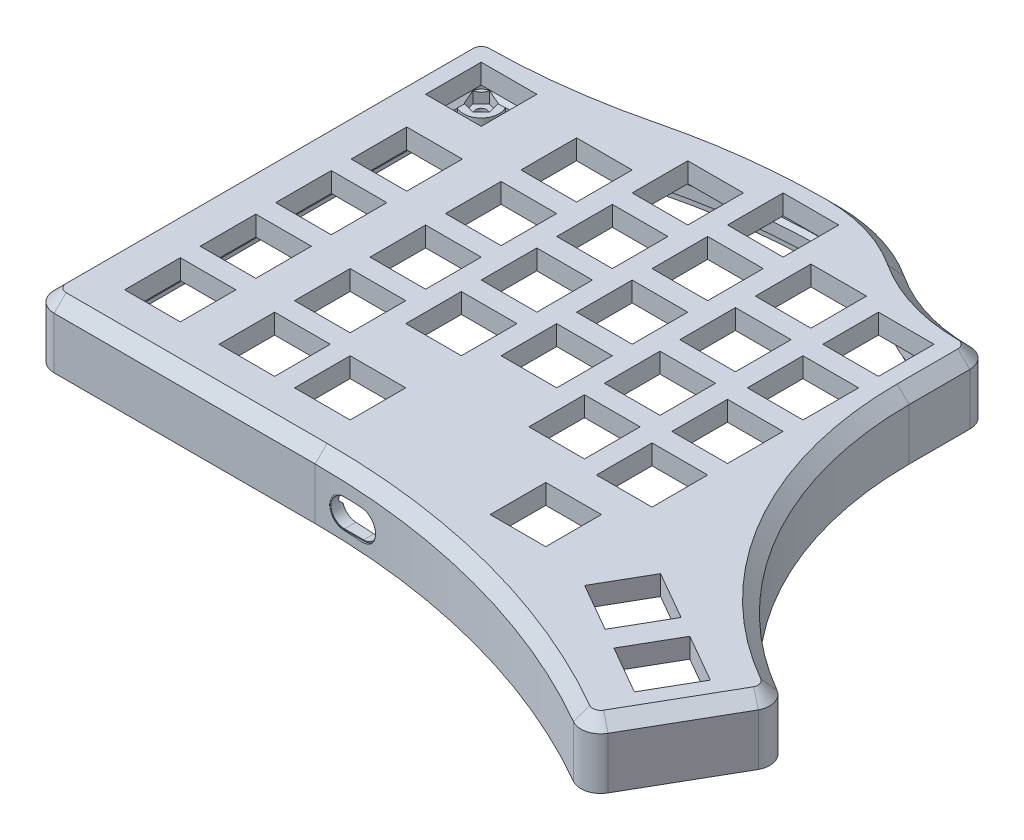
SolidWorks part; units mm, degrees
ref_plane "Front Plane" through (0, 0, 0) normal (0, 0, 1) x (1, 0, 0)
ref_plane "Top Plane" through (0, 0, 0) normal (0, 1, 0) x (1, 0, 0)
ref_plane "Right Plane" through (0, 0, 0) normal (1, 0, 0) x (0, 0, -1)
sketch "Main" plane through (0, 0, 0) normal (0, 1, 0) x (1, 0, 0)
  line L0 (6.4754, 3.5) -> (12.8, 6.5) construction
  line L1 (0, 0) -> (18, 0) construction
  line L2 (0, 0) -> (0, 18) construction
  line L3 (0, 18) -> (18, 18) construction
  line L4 (18, 0) -> (18, 18) construction
  line L5 (2, 16) -> (16, 16)
  line L6 (2, 16) -> (2, 2)
  line L7 (2, 2) -> (16, 2)
  line L8 (16, 16) -> (16, 2)
  line L18 (9, 9) -> (6.4754, 3.5) construction
  line L20 (9, 9) -> (12.8, 6.5) construction
  line L22 (25.4754, 12.5) -> (31.8, 15.5) construction
  line L23 (19, 9) -> (37, 9) construction
  line L24 (19, 9) -> (19, 27) construction
  line L25 (19, 27) -> (37, 27) construction
  line L26 (37, 9) -> (37, 27) construction
  line L27 (21, 25) -> (35, 25)
  line L28 (21, 25) -> (21, 11)
  line L29 (21, 11) -> (35, 11)
  line L30 (35, 25) -> (35, 11)
  line L31 (28, 18) -> (25.4754, 12.5) construction
  line L32 (28, 18) -> (31.8, 15.5) construction
  line L33 (44.4754, 17.5) -> (50.8, 20.5) construction
  line L34 (38, 14) -> (56, 14) construction
  line L35 (38, 14) -> (38, 32) construction
  line L36 (38, 32) -> (56, 32) construction
  line L37 (56, 14) -> (56, 32) construction
  line L38 (40, 30) -> (54, 30)
  line L39 (40, 30) -> (40, 16)
  line L40 (40, 16) -> (54, 16)
  line L41 (54, 30) -> (54, 16)
  line L42 (47, 23) -> (44.4754, 17.5) construction
  line L43 (47, 23) -> (50.8, 20.5) construction
  line L44 (63.4754, 5.5) -> (69.8, 8.5) construction
  line L45 (57, 2) -> (75, 2) construction
  line L46 (57, 2) -> (57, 20) construction
  line L47 (57, 20) -> (75, 20) construction
  line L48 (75, 2) -> (75, 20) construction
  line L49 (59, 18) -> (73, 18)
  line L50 (59, 18) -> (59, 4)
  line L51 (59, 4) -> (73, 4)
  line L52 (73, 18) -> (73, 4)
  line L53 (66, 11) -> (63.4754, 5.5) construction
  line L54 (66, 11) -> (69.8, 8.5) construction
  line L55 (82.4754, 3.5) -> (88.8, 6.5) construction
  line L56 (76, 0) -> (94, 0) construction
  line L57 (76, 0) -> (76, 18) construction
  line L58 (76, 18) -> (94, 18) construction
  line L59 (94, 0) -> (94, 18) construction
  line L60 (78, 16) -> (92, 16)
  line L61 (78, 16) -> (78, 2)
  line L62 (78, 2) -> (92, 2)
  line L63 (92, 16) -> (92, 2)
  line L64 (85, 9) -> (82.4754, 3.5) construction
  line L65 (85, 9) -> (88.8, 6.5) construction
  line L88 (2, -3) -> (16, -3)
  line L89 (2, -3) -> (2, -17)
  line L90 (2, -17) -> (16, -17)
  line L91 (16, -3) -> (16, -17)
  line L92 (21, 6) -> (35, 6)
  line L93 (21, 6) -> (21, -8)
  line L94 (21, -8) -> (35, -8)
  line L95 (35, 6) -> (35, -8)
  line L96 (40, 11) -> (54, 11)
  line L97 (40, 11) -> (40, -3)
  line L98 (40, -3) -> (54, -3)
  line L99 (54, 11) -> (54, -3)
  line L100 (59, -1) -> (73, -1)
  line L101 (59, -1) -> (59, -15)
  line L102 (59, -15) -> (73, -15)
  line L103 (73, -1) -> (73, -15)
  line L104 (78, -3) -> (92, -3)
  line L105 (78, -3) -> (78, -17)
  line L106 (78, -17) -> (92, -17)
  line L107 (92, -3) -> (92, -17)
  line L116 (6.4754, -15.5) -> (12.8, -12.5) construction
  line L117 (0, -19) -> (18, -19) construction
  line L118 (0, -19) -> (0, -1) construction
  line L119 (0, -1) -> (18, -1) construction
  line L120 (18, -19) -> (18, -1) construction
  line L121 (9, -10) -> (6.4754, -15.5) construction
  line L122 (9, -10) -> (12.8, -12.5) construction
  line L123 (25.4754, -6.5) -> (31.8, -3.5) construction
  line L124 (19, -10) -> (37, -10) construction
  line L125 (19, -10) -> (19, 8) construction
  line L126 (19, 8) -> (37, 8) construction
  line L127 (37, -10) -> (37, 8) construction
  line L128 (28, -1) -> (25.4754, -6.5) construction
  line L129 (28, -1) -> (31.8, -3.5) construction
  line L130 (44.4754, -1.5) -> (50.8, 1.5) construction
  line L131 (38, -5) -> (56, -5) construction
  line L132 (38, -5) -> (38, 13) construction
  line L133 (38, 13) -> (56, 13) construction
  line L134 (56, -5) -> (56, 13) construction
  line L135 (47, 4) -> (44.4754, -1.5) construction
  line L136 (47, 4) -> (50.8, 1.5) construction
  line L137 (63.4754, -13.5) -> (69.8, -10.5) construction
  line L138 (57, -17) -> (75, -17) construction
  line L139 (57, -17) -> (57, 1) construction
  line L140 (57, 1) -> (75, 1) construction
  line L141 (75, -17) -> (75, 1) construction
  line L142 (66, -8) -> (63.4754, -13.5) construction
  line L143 (66, -8) -> (69.8, -10.5) construction
  line L144 (82.4754, -15.5) -> (88.8, -12.5) construction
  line L145 (76, -19) -> (94, -19) construction
  line L146 (76, -19) -> (76, -1) construction
  line L147 (76, -1) -> (94, -1) construction
  line L148 (94, -19) -> (94, -1) construction
  line L149 (85, -10) -> (82.4754, -15.5) construction
  line L150 (85, -10) -> (88.8, -12.5) construction
  line L165 (2, -22) -> (16, -22)
  line L166 (2, -22) -> (2, -36)
  line L167 (2, -36) -> (16, -36)
  line L168 (16, -22) -> (16, -36)
  line L169 (21, -13) -> (35, -13)
  line L170 (21, -13) -> (21, -27)
  line L171 (21, -27) -> (35, -27)
  line L172 (35, -13) -> (35, -27)
  line L173 (40, -8) -> (54, -8)
  line L174 (40, -8) -> (40, -22)
  line L175 (40, -22) -> (54, -22)
  line L176 (54, -8) -> (54, -22)
  line L177 (59, -20) -> (73, -20)
  line L178 (59, -20) -> (59, -34)
  line L179 (59, -34) -> (73, -34)
  line L180 (73, -20) -> (73, -34)
  line L181 (78, -22) -> (92, -22)
  line L182 (78, -22) -> (78, -36)
  line L183 (78, -36) -> (92, -36)
  line L184 (92, -22) -> (92, -36)
  line L193 (6.4754, -34.5) -> (12.8, -31.5) construction
  line L194 (0, -38) -> (18, -38) construction
  line L195 (0, -38) -> (0, -20) construction
  line L196 (0, -20) -> (18, -20) construction
  line L197 (18, -38) -> (18, -20) construction
  line L198 (9, -29) -> (6.4754, -34.5) construction
  line L199 (9, -29) -> (12.8, -31.5) construction
  line L200 (25.4754, -25.5) -> (31.8, -22.5) construction
  line L201 (19, -29) -> (37, -29) construction
  line L202 (19, -29) -> (19, -11) construction
  line L203 (19, -11) -> (37, -11) construction
  line L204 (37, -29) -> (37, -11) construction
  line L205 (28, -20) -> (25.4754, -25.5) construction
  line L206 (28, -20) -> (31.8, -22.5) construction
  line L207 (44.4754, -20.5) -> (50.8, -17.5) construction
  line L208 (38, -24) -> (56, -24) construction
  line L209 (38, -24) -> (38, -6) construction
  line L210 (38, -6) -> (56, -6) construction
  line L211 (56, -24) -> (56, -6) construction
  line L212 (47, -15) -> (44.4754, -20.5) construction
  line L213 (47, -15) -> (50.8, -17.5) construction
  line L214 (63.4754, -32.5) -> (69.8, -29.5) construction
  line L215 (57, -36) -> (75, -36) construction
  line L216 (57, -36) -> (57, -18) construction
  line L217 (57, -18) -> (75, -18) construction
  line L218 (75, -36) -> (75, -18) construction
  line L219 (66, -27) -> (63.4754, -32.5) construction
  line L220 (66, -27) -> (69.8, -29.5) construction
  line L221 (82.4754, -34.5) -> (88.8, -31.5) construction
  line L222 (76, -38) -> (94, -38) construction
  line L223 (76, -38) -> (76, -20) construction
  line L224 (76, -20) -> (94, -20) construction
  line L225 (94, -38) -> (94, -20) construction
  line L226 (85, -29) -> (82.4754, -34.5) construction
  line L227 (85, -29) -> (88.8, -31.5) construction
  line L242 (2, -41) -> (16, -41)
  line L243 (2, -41) -> (2, -55)
  line L244 (2, -55) -> (16, -55)
  line L245 (16, -41) -> (16, -55)
  line L246 (21, -32) -> (35, -32)
  line L247 (21, -32) -> (21, -46)
  line L248 (21, -46) -> (35, -46)
  line L249 (35, -32) -> (35, -46)
  line L250 (40, -27) -> (54, -27)
  line L251 (40, -27) -> (40, -41)
  line L252 (40, -41) -> (54, -41)
  line L253 (54, -27) -> (54, -41)
  line L254 (59, -39) -> (73, -39)
  line L255 (59, -39) -> (59, -53)
  line L256 (59, -53) -> (73, -53)
  line L257 (73, -39) -> (73, -53)
  line L258 (78, -41) -> (92, -41)
  line L259 (78, -41) -> (78, -55)
  line L260 (78, -55) -> (92, -55)
  line L261 (92, -41) -> (92, -55)
  line L270 (6.4754, -53.5) -> (12.8, -50.5) construction
  line L271 (0, -57) -> (18, -57) construction
  line L272 (0, -57) -> (0, -39) construction
  line L273 (0, -39) -> (18, -39) construction
  line L274 (18, -57) -> (18, -39) construction
  line L275 (9, -48) -> (6.4754, -53.5) construction
  line L276 (9, -48) -> (12.8, -50.5) construction
  line L277 (25.4754, -44.5) -> (31.8, -41.5) construction
  line L278 (19, -48) -> (37, -48) construction
  line L279 (19, -48) -> (19, -30) construction
  line L280 (19, -30) -> (37, -30) construction
  line L281 (37, -48) -> (37, -30) construction
  line L282 (28, -39) -> (25.4754, -44.5) construction
  line L283 (28, -39) -> (31.8, -41.5) construction
  line L284 (44.4754, -39.5) -> (50.8, -36.5) construction
  line L285 (38, -43) -> (56, -43) construction
  line L286 (38, -43) -> (38, -25) construction
  line L287 (38, -25) -> (56, -25) construction
  line L288 (56, -43) -> (56, -25) construction
  line L289 (47, -34) -> (44.4754, -39.5) construction
  line L290 (47, -34) -> (50.8, -36.5) construction
  line L291 (63.4754, -51.5) -> (69.8, -48.5) construction
  line L292 (57, -55) -> (75, -55) construction
  line L293 (57, -55) -> (57, -37) construction
  line L294 (57, -37) -> (75, -37) construction
  line L295 (75, -55) -> (75, -37) construction
  line L296 (66, -46) -> (63.4754, -51.5) construction
  line L297 (66, -46) -> (69.8, -48.5) construction
  line L298 (82.4754, -53.5) -> (88.8, -50.5) construction
  line L299 (76, -57) -> (94, -57) construction
  line L300 (76, -57) -> (76, -39) construction
  line L301 (76, -39) -> (94, -39) construction
  line L302 (94, -57) -> (94, -39) construction
  line L303 (85, -48) -> (82.4754, -53.5) construction
  line L304 (85, -48) -> (88.8, -50.5) construction
  line L312 (6.4754, -72.5) -> (12.8, -69.5) construction
  line L313 (0, -76) -> (18, -76) construction
  line L314 (0, -76) -> (0, -58) construction
  line L315 (0, -58) -> (18, -58) construction
  line L316 (18, -76) -> (18, -58) construction
  line L317 (2, -60) -> (16, -60)
  line L318 (2, -60) -> (2, -74)
  line L323 (21, -60) -> (35, -60)
  line L324 (21, -60) -> (21, -74)
  line L325 (21, -74) -> (35, -74)
  line L326 (35, -60) -> (35, -74)
  line L327 (25.4754, -72.5) -> (31.8, -69.5) construction
  line L328 (19, -76) -> (37, -76) construction
  line L329 (19, -76) -> (19, -58) construction
  line L330 (-22.0246, 8) -> (-15.7, 11) construction
  line L331 (-28.5, 4.5) -> (-10.5, 4.5) construction
  line L332 (-28.5, 4.5) -> (-28.5, 22.5) construction
  line L333 (-28.5, 22.5) -> (-10.5, 22.5) construction
  line L334 (-10.5, 4.5) -> (-10.5, 22.5) construction
  line L335 (-26.5, 20.5) -> (-12.5, 20.5)
  line L336 (-26.5, 20.5) -> (-26.5, 6.5)
  line L337 (-26.5, 6.5) -> (-12.5, 6.5)
  line L338 (-12.5, 20.5) -> (-12.5, 6.5)
  line L339 (-19.5, 13.5) -> (-22.0246, 8) construction
  line L340 (-19.5, 13.5) -> (-15.7, 11) construction
  line L341 (-21.75, -41) -> (-7.75, -41)
  line L342 (-21.75, -41) -> (-21.75, -55)
  line L343 (-21.75, -55) -> (-7.75, -55)
  line L344 (-7.75, -41) -> (-7.75, -55)
  line L345 (-17.2746, -53.5) -> (-10.95, -50.5) construction
  line L346 (-28.5, -57) -> (-1, -57) construction
  line L347 (-28.5, -57) -> (-28.5, -39) construction
  line L348 (-28.5, -39) -> (-1, -39) construction
  line L349 (-1, -57) -> (-1, -39) construction
  line L350 (-14.75, -48) -> (-17.2746, -53.5) construction
  line L351 (-14.75, -48) -> (-10.95, -50.5) construction
  line L352 (-21.75, -22) -> (-7.75, -22)
  line L353 (-21.75, -22) -> (-21.75, -36)
  line L354 (2, -74) -> (16, -74)
  line L355 (16, -60) -> (16, -74)
  line L356 (9, -67) -> (6.4754, -72.5) construction
  line L357 (9, -67) -> (12.8, -69.5) construction
  line L358 (-17.2746, -72.5) -> (-10.95, -69.5) construction
  line L359 (-28.5, -76) -> (-1, -76) construction
  line L360 (-28.5, -76) -> (-28.5, -58) construction
  line L361 (-28.5, -58) -> (-1, -58) construction
  line L362 (-1, -76) -> (-1, -58) construction
  line L363 (-21.75, -60) -> (-7.75, -60)
  line L364 (-21.75, -60) -> (-21.75, -74)
  line L365 (-21.75, -74) -> (-7.75, -74)
  line L366 (-7.75, -60) -> (-7.75, -74)
  line L367 (-14.75, -67) -> (-17.2746, -72.5) construction
  line L368 (-14.75, -67) -> (-10.95, -69.5) construction
  line L369 (-21.75, -36) -> (-7.75, -36)
  line L370 (-7.75, -22) -> (-7.75, -36)
  line L371 (-17.2746, -34.5) -> (-10.95, -31.5) construction
  line L372 (-28.5, -38) -> (-1, -38) construction
  line L373 (-28.5, -38) -> (-28.5, -20) construction
  line L374 (-28.5, -20) -> (-1, -20) construction
  line L375 (-1, -38) -> (-1, -20) construction
  line L376 (-14.75, -29) -> (-17.2746, -34.5) construction
  line L377 (-14.75, -29) -> (-10.95, -31.5) construction
  line L378 (-21.75, -3) -> (-7.75, -3)
  line L379 (-21.75, -3) -> (-21.75, -17)
  line L380 (-21.75, -17) -> (-7.75, -17)
  line L381 (-7.75, -3) -> (-7.75, -17)
  line L382 (-17.2746, -15.5) -> (-10.95, -12.5) construction
  line L383 (-28.5, -19) -> (-1, -19) construction
  line L384 (-28.5, -19) -> (-28.5, -1) construction
  line L385 (-28.5, -1) -> (-1, -1) construction
  line L386 (-1, -19) -> (-1, -1) construction
  line L387 (-14.75, -10) -> (-17.2746, -15.5) construction
  line L388 (-14.75, -10) -> (-10.95, -12.5) construction
  line L393 (109.2068, -61.578) -> (124.8116, -70.5498) construction
  line L394 (109.2068, -61.578) -> (95.5, -85.4186) construction
  line L398 (124.8116, -70.5498) -> (111.1047, -94.3903) construction
  line L402 (77.7254, -75.5) -> (84.05, -72.5) construction
  line L403 (66.5, -79) -> (94, -79) construction
  line L404 (66.5, -79) -> (66.5, -61) construction
  line L405 (66.5, -61) -> (94, -61) construction
  line L406 (94, -79) -> (94, -61) construction
  line L407 (73.25, -63) -> (87.25, -63)
  line L408 (73.25, -63) -> (73.25, -77)
  line L409 (73.25, -77) -> (87.25, -77)
  line L410 (87.25, -63) -> (87.25, -77)
  line L411 (80.25, -70) -> (77.7254, -75.5) construction
  line L412 (80.25, -70) -> (84.05, -72.5) construction
  line L413 (95.5, -85.4186) -> (111.1047, -94.3903) construction
  line L414 (95.5, -85.4186) -> (124.8116, -70.5498) construction
  line L415 (80.25, -130) -> (110.1558, -77.9842) construction
  line L416 (107.5763, -68.4267) -> (119.7133, -75.4047)
  line L417 (107.5763, -68.4267) -> (100.5983, -80.5637)
  line L418 (119.7133, -75.4047) -> (112.7353, -87.5417)
  line L419 (100.5983, -80.5637) -> (112.7353, -87.5417)
  line L420 (107.5763, -68.4267) -> (112.7353, -87.5417) construction
  line L421 (105.2258, -81.494) -> (110.1558, -77.9842) construction
  line L422 (110.1558, -77.9842) -> (112.204, -82.0455) construction
  line L423 (112.204, -82.0455) -> (105.2258, -81.494) construction
  line L424 (126.5454, -71.5466) -> (142.1502, -80.5184) construction
  line L425 (126.5454, -71.5466) -> (112.8386, -95.3872) construction
  line L426 (142.1502, -80.5184) -> (128.4433, -104.3589) construction
  line L427 (112.8386, -95.3872) -> (128.4433, -104.3589) construction
  line L428 (112.8386, -95.3872) -> (142.1502, -80.5184) construction
  line L430 (124.9149, -78.3953) -> (137.0519, -85.3733)
  line L431 (124.9149, -78.3953) -> (117.9369, -90.5323)
  line L432 (137.0519, -85.3733) -> (130.0739, -97.5103)
  line L433 (117.9369, -90.5323) -> (130.0739, -97.5103)
  line L434 (124.9149, -78.3953) -> (130.0739, -97.5103) construction
  line L435 (122.5644, -91.4626) -> (127.4944, -87.9528) construction
  line L436 (127.4944, -87.9528) -> (129.5426, -92.0141) construction
  line L437 (129.5426, -92.0141) -> (122.5644, -91.4626) construction
  line L448 (19, -58) -> (37, -58) construction
  line L449 (37, -76) -> (37, -58) construction
  line L450 (28, -67) -> (25.4754, -72.5) construction
  line L451 (28, -67) -> (31.8, -69.5) construction
  circle A0 centre (9, 9) radius 2 construction
  circle A1 centre (6.4754, 3.5) radius 1.5 construction
  circle A2 centre (12.8, 6.5) radius 1.5 construction
  circle A6 centre (28, 18) radius 2 construction
  circle A7 centre (25.4754, 12.5) radius 1.5 construction
  circle A8 centre (31.8, 15.5) radius 1.5 construction
  circle A9 centre (47, 23) radius 2 construction
  circle A10 centre (44.4754, 17.5) radius 1.5 construction
  circle A11 centre (50.8, 20.5) radius 1.5 construction
  circle A12 centre (66, 11) radius 2 construction
  circle A13 centre (63.4754, 5.5) radius 1.5 construction
  circle A14 centre (69.8, 8.5) radius 1.5 construction
  circle A15 centre (85, 9) radius 2 construction
  circle A16 centre (82.4754, 3.5) radius 1.5 construction
  circle A17 centre (88.8, 6.5) radius 1.5 construction
  circle A24 centre (9, -10) radius 2 construction
  circle A25 centre (6.4754, -15.5) radius 1.5 construction
  circle A26 centre (12.8, -12.5) radius 1.5 construction
  circle A27 centre (28, -1) radius 2 construction
  circle A28 centre (25.4754, -6.5) radius 1.5 construction
  circle A29 centre (31.8, -3.5) radius 1.5 construction
  circle A30 centre (47, 4) radius 2 construction
  circle A31 centre (44.4754, -1.5) radius 1.5 construction
  circle A32 centre (50.8, 1.5) radius 1.5 construction
  circle A33 centre (66, -8) radius 2 construction
  circle A34 centre (63.4754, -13.5) radius 1.5 construction
  circle A35 centre (69.8, -10.5) radius 1.5 construction
  circle A36 centre (85, -10) radius 2 construction
  circle A37 centre (82.4754, -15.5) radius 1.5 construction
  circle A38 centre (88.8, -12.5) radius 1.5 construction
  circle A45 centre (9, -29) radius 2 construction
  circle A46 centre (6.4754, -34.5) radius 1.5 construction
  circle A47 centre (12.8, -31.5) radius 1.5 construction
  circle A48 centre (28, -20) radius 2 construction
  circle A49 centre (25.4754, -25.5) radius 1.5 construction
  circle A50 centre (31.8, -22.5) radius 1.5 construction
  circle A51 centre (47, -15) radius 2 construction
  circle A52 centre (44.4754, -20.5) radius 1.5 construction
  circle A53 centre (50.8, -17.5) radius 1.5 construction
  circle A54 centre (66, -27) radius 2 construction
  circle A55 centre (63.4754, -32.5) radius 1.5 construction
  circle A56 centre (69.8, -29.5) radius 1.5 construction
  circle A57 centre (85, -29) radius 2 construction
  circle A58 centre (82.4754, -34.5) radius 1.5 construction
  circle A59 centre (88.8, -31.5) radius 1.5 construction
  circle A63 centre (9, -67) radius 2 construction
  circle A64 centre (6.4754, -72.5) radius 1.5 construction
  circle A65 centre (12.8, -69.5) radius 1.5 construction
  circle A66 centre (9, -48) radius 2 construction
  circle A67 centre (6.4754, -53.5) radius 1.5 construction
  circle A68 centre (12.8, -50.5) radius 1.5 construction
  circle A69 centre (28, -39) radius 2 construction
  circle A70 centre (25.4754, -44.5) radius 1.5 construction
  circle A71 centre (31.8, -41.5) radius 1.5 construction
  circle A72 centre (47, -34) radius 2 construction
  circle A73 centre (44.4754, -39.5) radius 1.5 construction
  circle A74 centre (50.8, -36.5) radius 1.5 construction
  circle A75 centre (66, -46) radius 2 construction
  circle A76 centre (63.4754, -51.5) radius 1.5 construction
  circle A77 centre (69.8, -48.5) radius 1.5 construction
  circle A78 centre (85, -48) radius 2 construction
  circle A79 centre (82.4754, -53.5) radius 1.5 construction
  circle A80 centre (88.8, -50.5) radius 1.5 construction
  circle A81 centre (-14.75, -67) radius 2 construction
  circle A82 centre (-17.2746, -72.5) radius 1.5 construction
  circle A83 centre (-10.95, -69.5) radius 1.5 construction
  circle A84 centre (28, -67) radius 2 construction
  circle A85 centre (25.4754, -72.5) radius 1.5 construction
  circle A86 centre (31.8, -69.5) radius 1.5 construction
  circle A87 centre (-19.5, 13.5) radius 2 construction
  circle A88 centre (-22.0246, 8) radius 1.5 construction
  circle A89 centre (-15.7, 11) radius 1.5 construction
  circle A90 centre (-14.75, -48) radius 2 construction
  circle A91 centre (-17.2746, -53.5) radius 1.5 construction
  circle A92 centre (-10.95, -50.5) radius 1.5 construction
  circle A93 centre (-14.75, -29) radius 2 construction
  circle A94 centre (-17.2746, -34.5) radius 1.5 construction
  circle A95 centre (-10.95, -31.5) radius 1.5 construction
  circle A96 centre (-14.75, -10) radius 2 construction
  circle A97 centre (-17.2746, -15.5) radius 1.5 construction
  circle A98 centre (-10.95, -12.5) radius 1.5 construction
  circle A102 centre (80.25, -70) radius 2 construction
  circle A103 centre (77.7254, -75.5) radius 1.5 construction
  circle A104 centre (84.05, -72.5) radius 1.5 construction
  circle A105 centre (80.25, -130) radius 60 construction
  circle A106 centre (110.1558, -77.9842) radius 2 construction
  circle A107 centre (105.2258, -81.494) radius 1.5 construction
  circle A108 centre (112.204, -82.0455) radius 1.5 construction
  circle A109 centre (127.4944, -87.9528) radius 2 construction
  circle A110 centre (122.5644, -91.4626) radius 1.5 construction
  circle A111 centre (129.5426, -92.0141) radius 1.5 construction
  circle A112 centre (62, -66) radius 1.5 construction
  point P9 (9, 16)
  point P10 (9, 18)
  point P11 (2, 9)
  point P12 (0, 9)
  point P30 (28, 25)
  point P31 (28, 27)
  point P32 (21, 18)
  point P33 (19, 18)
  point P46 (47, 30)
  point P47 (47, 32)
  point P48 (40, 23)
  point P49 (38, 23)
  point P64 (66, 18)
  point P65 (66, 20)
  point P66 (59, 11)
  point P67 (57, 11)
  point P82 (85, 16)
  point P83 (85, 18)
  point P84 (78, 9)
  point P85 (76, 9)
  point P102 (9, -60)
  point P103 (9, -58)
  point P104 (2, -67)
  point P105 (0, -67)
  point P124 (-14.75, -60)
  point P125 (-14.75, -58)
  point P126 (-21.75, -67)
  point P127 (-28.5, -67)
  point P297 (-19.5, 20.5)
  point P298 (-19.5, 22.5)
  point P299 (-26.5, 13.5)
  point P300 (-28.5, 13.5)
  point P423 (103.3024, -89.9045)
  point P444 (80.25, -63)
  point P445 (80.25, -61)
  point P446 (73.25, -70)
  point P447 (66.5, -70)
  dimension "D6" = 4
  dimension "D7" = 3
  dimension "D10" = 1
  dimension "D11" = 12
  dimension "D21" = 9.5
  dimension "D22" = 1.5
  dimension "D26" = 120
  dimension "D28" = 3
  dimension "D1" = 18
  dimension "D2" = 14
  dimension "D3" = 3.2
  dimension "D4" = 4.5
  dimension "D5" = 7
  dimension "D8" = 1
  dimension "D9" = 5
  dimension "D12" = 1
  dimension "D13" = 9
  dimension "D14" = 1
  dimension "D15" = 2
  dimension "D16" = 2
  dimension "D17" = 27.5
  dimension "D18" = 1
  dimension "D20" = 1
  dimension "D24" = 1
  dimension "D25" = 8
  dimension "D27" = 2
  dimension "D29" = 15
  dimension "D30" = 32
  dimension "D19" = 4
  dimension "D23" = 4
sketch "Sketch1" plane through (0, 0, 0) normal (0, 1, 0) x (1, 0, 0)
  line L0 (-33.5, 22.5) -> (-33.5, -80)
  line L1 (-28.5, -85) -> (37.2039, -85)
  line L2 (132.778, -106.8511) -> (146.594, -82.8206)
  line L3 (99, 2.7142) -> (99, 18)
  line L6 (-28.5, -76) -> (-1, -76) construction
  line L7 (-28.5, -76) -> (-28.5, -58) construction
  line L8 (144.6447, -76.1796) -> (94, -47.0621) construction
  line L9 (142.1502, -80.5184) -> (128.4433, -104.3589) construction
  line L10 (94, 0) -> (94, 18) construction
  line L11 (94, -57) -> (94, -39) construction
  line L12 (128.4433, -104.3589) -> (125.9512, -108.6936) construction
  line L13 (109.2068, -61.578) -> (124.8116, -70.5498) construction
  line L14 (125.9512, -108.6936) -> (74.3045, -79) construction
  line L15 (66.5, -79) -> (94, -79) construction
  line L16 (38, 32) -> (56, 32) construction
  line L17 (95.5, -85.4186) -> (111.1047, -94.3903) construction
  line L18 (47, 37) -> (47, 32) construction
  line L19 (47, 37) -> (-33.5, 37) construction
  line L20 (94, 23) -> (56, 23) construction
  line L21 (56, 14) -> (56, 32) construction
  line L22 (-31.5, 22.5) -> (-31.5, -80) construction
  line L24 (-28.5, -83) -> (37.2039, -83) construction
  line L25 (131.0441, -105.8542) -> (144.8356, -81.8665) construction
  line L26 (97, 2.7142) -> (97, 18) construction
  line L39 (107.5763, -68.4267) -> (119.7133, -75.4047)
  line L40 (-26.5, 20.5) -> (-12.5, 20.5)
  line L41 (-26.5, 20.5) -> (-26.5, 6.5)
  line L42 (-26.5, 6.5) -> (-12.5, 6.5)
  line L43 (-12.5, 20.5) -> (-12.5, 6.5)
  line L44 (-21.75, -3) -> (-7.75, -3)
  line L45 (-21.75, -3) -> (-21.75, -17)
  line L46 (-21.75, -17) -> (-7.75, -17)
  line L47 (-7.75, -3) -> (-7.75, -17)
  line L48 (-21.75, -22) -> (-7.75, -22)
  line L49 (-21.75, -22) -> (-21.75, -36)
  line L50 (-21.75, -36) -> (-7.75, -36)
  line L51 (-7.75, -22) -> (-7.75, -36)
  line L52 (-21.75, -41) -> (-7.75, -41)
  line L53 (-21.75, -41) -> (-21.75, -55)
  line L54 (-21.75, -55) -> (-7.75, -55)
  line L55 (-7.75, -41) -> (-7.75, -55)
  line L56 (-21.75, -60) -> (-7.75, -60)
  line L57 (-21.75, -60) -> (-21.75, -74)
  line L58 (-21.75, -74) -> (-7.75, -74)
  line L59 (-7.75, -60) -> (-7.75, -74)
  line L60 (2, 16) -> (16, 16)
  line L61 (2, 16) -> (2, 2)
  line L62 (2, 2) -> (16, 2)
  line L63 (16, 16) -> (16, 2)
  line L64 (2, -3) -> (16, -3)
  line L65 (2, -3) -> (2, -17)
  line L66 (2, -17) -> (16, -17)
  line L67 (16, -3) -> (16, -17)
  line L68 (2, -22) -> (16, -22)
  line L69 (2, -22) -> (2, -36)
  line L70 (2, -36) -> (16, -36)
  line L71 (16, -22) -> (16, -36)
  line L72 (2, -41) -> (16, -41)
  line L73 (2, -41) -> (2, -55)
  line L74 (2, -55) -> (16, -55)
  line L75 (16, -41) -> (16, -55)
  line L76 (2, -60) -> (16, -60)
  line L77 (2, -60) -> (2, -74)
  line L78 (2, -74) -> (16, -74)
  line L79 (16, -60) -> (16, -74)
  line L80 (21, -60) -> (35, -60)
  line L81 (21, -60) -> (21, -74)
  line L82 (21, -74) -> (35, -74)
  line L83 (35, -60) -> (35, -74)
  line L84 (21, -32) -> (35, -32)
  line L85 (21, -32) -> (21, -46)
  line L86 (21, -46) -> (35, -46)
  line L87 (35, -32) -> (35, -46)
  line L88 (21, 25) -> (35, 25)
  line L89 (21, 25) -> (21, 11)
  line L90 (21, 11) -> (35, 11)
  line L91 (35, 25) -> (35, 11)
  line L92 (21, 6) -> (35, 6)
  line L93 (21, 6) -> (21, -8)
  line L94 (21, -8) -> (35, -8)
  line L95 (35, 6) -> (35, -8)
  line L96 (21, -13) -> (35, -13)
  line L97 (21, -13) -> (21, -27)
  line L98 (21, -27) -> (35, -27)
  line L99 (35, -13) -> (35, -27)
  line L100 (40, 30) -> (54, 30)
  line L101 (40, 30) -> (40, 16)
  line L102 (40, 16) -> (54, 16)
  line L103 (54, 30) -> (54, 16)
  line L104 (40, 11) -> (54, 11)
  line L105 (40, 11) -> (40, -3)
  line L106 (40, -3) -> (54, -3)
  line L107 (54, 11) -> (54, -3)
  line L108 (40, -8) -> (54, -8)
  line L109 (40, -8) -> (40, -22)
  line L110 (40, -22) -> (54, -22)
  line L111 (54, -8) -> (54, -22)
  line L112 (40, -27) -> (54, -27)
  line L113 (40, -27) -> (40, -41)
  line L114 (40, -41) -> (54, -41)
  line L115 (54, -27) -> (54, -41)
  line L116 (59, 18) -> (73, 18)
  line L117 (59, 18) -> (59, 4)
  line L118 (59, 4) -> (73, 4)
  line L119 (73, 18) -> (73, 4)
  line L120 (78, 16) -> (92, 16)
  line L121 (78, 16) -> (78, 2)
  line L122 (78, 2) -> (92, 2)
  line L123 (92, 16) -> (92, 2)
  line L124 (59, -1) -> (73, -1)
  line L125 (59, -1) -> (59, -15)
  line L126 (59, -15) -> (73, -15)
  line L127 (73, -1) -> (73, -15)
  line L128 (78, -3) -> (92, -3)
  line L129 (78, -3) -> (78, -17)
  line L130 (78, -17) -> (92, -17)
  line L131 (92, -3) -> (92, -17)
  line L132 (59, -20) -> (73, -20)
  line L133 (59, -20) -> (59, -34)
  line L134 (59, -34) -> (73, -34)
  line L135 (73, -20) -> (73, -34)
  line L136 (78, -22) -> (92, -22)
  line L137 (78, -22) -> (78, -36)
  line L138 (78, -36) -> (92, -36)
  line L139 (92, -22) -> (92, -36)
  line L140 (59, -39) -> (73, -39)
  line L141 (59, -39) -> (59, -53)
  line L142 (59, -53) -> (73, -53)
  line L143 (73, -39) -> (73, -53)
  line L144 (78, -41) -> (92, -41)
  line L145 (78, -41) -> (78, -55)
  line L146 (78, -55) -> (92, -55)
  line L147 (92, -41) -> (92, -55)
  line L148 (73.25, -63) -> (87.25, -63)
  line L149 (73.25, -63) -> (73.25, -77)
  line L150 (73.25, -77) -> (87.25, -77)
  line L151 (87.25, -63) -> (87.25, -77)
  line L152 (107.5763, -68.4267) -> (100.5983, -80.5637)
  line L153 (119.7133, -75.4047) -> (112.7353, -87.5417)
  line L154 (100.5983, -80.5637) -> (112.7353, -87.5417)
  line L155 (124.9149, -78.3953) -> (137.0519, -85.3733)
  line L156 (124.9149, -78.3953) -> (117.9369, -90.5323)
  line L157 (137.0519, -85.3733) -> (130.0739, -97.5103)
  line L158 (117.9369, -90.5323) -> (130.0739, -97.5103)
  arc A0 (37.2039, -85) -> (125.9512, -108.6936) centre (37.2039, -263.0538) cw
  arc A4 (94, 23) -> (70.5, 30) centre (94, 65.9464) cw
  arc A5 (70.5, 30) -> (47, 37) centre (47, -5.9464) ccw
  arc A6 (47, 37) -> (8.1496, 32.2427) centre (47, -124.0147) ccw
  arc A7 (8.1496, 32.2427) -> (-28.5663, 27.4996) centre (-30.7009, 188.5001) cw
  arc A10 (125.9512, -108.6936) -> (132.778, -106.8511) centre (128.4433, -104.3589) ccw
  arc A11 (-33.5, -80) -> (-28.5, -85) centre (-28.5, -80) ccw
  arc A14 (146.594, -82.8206) -> (144.6447, -76.1796) centre (142.1502, -80.5184) ccw
  arc A15 (144.6447, -76.1796) -> (99, 2.7142) centre (190.0036, 2.7142) cw
  arc A16 (99, 18) -> (94, 23) centre (94, 18) ccw
  arc A17 (-33.5, 22.5) -> (-28.5663, 27.4996) centre (-28.5, 22.5) cw
  arc A18 (8.6321, 30.3018) -> (-28.5398, 25.4997) centre (-30.7009, 188.5001) cw construction
  arc A19 (-31.5, 22.5) -> (-28.5398, 25.4997) centre (-28.5, 22.5) cw construction
  arc A20 (-31.5, -80) -> (-28.5, -83) centre (-28.5, -80) ccw construction
  arc A21 (37.2039, -83) -> (126.9481, -106.9597) centre (37.2039, -263.0538) cw construction
  arc A22 (126.9481, -106.9597) -> (131.0441, -105.8542) centre (128.4433, -104.3589) ccw construction
  arc A23 (144.8356, -81.8665) -> (143.6478, -77.9134) centre (142.1502, -80.5184) ccw construction
  arc A24 (143.6478, -77.9134) -> (97, 2.7142) centre (190.0036, 2.7142) cw construction
  arc A25 (97, 18) -> (94, 21) centre (94, 18) ccw construction
  arc A26 (94, 21) -> (69.4056, 28.326) centre (94, 65.9464) cw construction
  arc A27 (69.4056, 28.326) -> (47, 35) centre (47, -5.9464) ccw construction
  arc A28 (47, 35) -> (8.6321, 30.3018) centre (47, -124.0147) ccw construction
  dimension "D1" = 9
  dimension "D2" = 5
  dimension "D7" = 5.0048
  dimension "D8" = 5
  dimension "D3" = 5
  dimension "D4" = 5
  dimension "D5" = 5
  dimension "D6" = 5
  dimension "D9" = 2
extrude "Main_plate" add sketch "Sketch1" against normal blind 5
chamfer "Main_plate_chamfer" distance 3 15 edges at (146.9524, 0, 79.1088) (111.2334, 0, 42.859) (99, 0, -10.3571) (97.5355, 0, -21.5355) (81.7398, 0, -24.7872) (59.2602, 0, -35.2128) (27.4297, 0, -35.8063) (-10.0716, 0, -28.8124) (-32.0589, 0, -26.012) (139.686, 0, 94.8358) (-33.5, 0, 28.75) (129.7462, 0, 109.1862) (-32.0355, 0, 83.5355) (83.1318, 0, 91.0253) (4.352, 0, 85)
sketch "Sketch3" plane through (0, -5, 0) normal (0, -1, 0) x (1, 0, 0)
  line L0 (-28.5, 85) -> (37.2039, 85)
  line L1 (132.778, 106.8511) -> (146.594, 82.8206)
  line L2 (-33.5, 80) -> (-33.5, -22.5)
  line L3 (99, -18) -> (99, -2.7142)
  line L4 (-28.5, 83) -> (37.2039, 83)
  line L5 (131.0441, 105.8542) -> (144.8356, 81.8665)
  line L6 (97, -18) -> (97, -2.7142)
  line L7 (-31.5, 80) -> (-31.5, -22.5)
  arc A0 (37.2039, 85) -> (125.9512, 108.6936) centre (37.2039, 263.0538) ccw
  arc A1 (125.9512, 108.6936) -> (132.778, 106.8511) centre (128.4433, 104.3589) cw
  arc A2 (-28.5, 85) -> (-33.5, 80) centre (-28.5, 80) ccw
  arc A3 (-33.5, -22.5) -> (-28.5663, -27.4996) centre (-28.5, -22.5) ccw
  arc A4 (-28.5663, -27.4996) -> (8.1496, -32.2427) centre (-30.7009, -188.5001) cw
  arc A5 (8.1496, -32.2427) -> (47, -37) centre (47, 124.0147) ccw
  arc A6 (47, -37) -> (70.5, -30) centre (47, 5.9464) ccw
  arc A7 (70.5, -30) -> (94, -23) centre (94, -65.9464) cw
  arc A8 (94, -23) -> (99, -18) centre (94, -18) ccw
  arc A10 (144.6447, 76.1796) -> (146.594, 82.8206) centre (142.1502, 80.5184) ccw
  arc A11 (144.6447, 76.1796) -> (99, -2.7142) centre (190.0036, -2.7142) ccw
  arc A12 (37.2039, 83) -> (126.9481, 106.9597) centre (37.2039, 263.0538) ccw
  arc A13 (126.9481, 106.9597) -> (131.0441, 105.8542) centre (128.4433, 104.3589) cw
  arc A14 (143.6478, 77.9134) -> (144.8356, 81.8665) centre (142.1502, 80.5184) ccw
  arc A15 (143.6478, 77.9134) -> (97, -2.7142) centre (190.0036, -2.7142) ccw
  arc A16 (94, -21) -> (97, -18) centre (94, -18) ccw
  arc A17 (69.4056, -28.326) -> (94, -21) centre (94, -65.9464) cw
  arc A18 (47, -35) -> (69.4056, -28.326) centre (47, 5.9464) ccw
  arc A19 (8.6321, -30.3018) -> (47, -35) centre (47, 124.0147) ccw
  arc A20 (-28.5398, -25.4997) -> (8.6321, -30.3018) centre (-30.7009, -188.5001) cw
  arc A21 (-31.5, -22.5) -> (-28.5398, -25.4997) centre (-28.5, -22.5) ccw
  arc A22 (-28.5, 83) -> (-31.5, 80) centre (-28.5, 80) ccw
  dimension "D1" = 2
extrude "Wall" add sketch "Sketch3" along normal blind 11
sketch "Sketch4" plane through (0, -5, 0) normal (0, -1, 0) x (1, 0, 0)
  line L0 (47, 41) -> (47, 83.2667) construction
  line L1 (40, 41) -> (54, 41) construction
  line L2 (54.62, 81) -> (54.62, 48) construction
  line L3 (37.2039, 83) -> (-28.5, 83) construction
  line L4 (40.88, 48) -> (37.88, 48)
  line L5 (53.12, 81) -> (56.12, 81)
  line L6 (53.12, 81) -> (53.12, 48)
  line L7 (53.12, 48) -> (56.12, 48)
  line L8 (56.12, 81) -> (56.12, 48)
  line L9 (37.88, 81) -> (37.88, 48)
  line L10 (40.88, 81) -> (40.88, 48)
  line L11 (40.88, 81) -> (37.88, 81)
  arc A0 (37.2039, 83) -> (126.9481, 106.9597) centre (37.2039, 263.0538) ccw construction
  point P15 (54.62, 81)
  dimension "D1" = 7.62
  dimension "D2" = 2
  dimension "D3" = 33
  dimension "D4" = 3
extrude "For_pins_recess" cut sketch "Sketch4" against normal blind 2
ref_plane "Plane1" through (0, -14, 0) normal (0, -1, 0) x (-1, 0, 0)
sketch "Sketch8" plane through (0, -14, 0) normal (0, -1, 0) x (-1, 0, 0)
  line L41 (-143.9531, -81.395) -> (-130.1772, -105.3558)
  line L42 (-96, 18) -> (-96, 2.7142)
  line L43 (30.5, -80) -> (30.5, 22.5)
  line L44 (-37.2039, -82) -> (28.5, -82)
  line L45 (-143.9531, -81.395) -> (-130.1772, -105.3558)
  line L46 (-96, 18) -> (-96, 2.7142)
  line L47 (30.5, -80) -> (30.5, 22.5)
  line L48 (-37.2039, -82) -> (28.5, -82)
  line L86 (-144.8356, -81.8665) -> (-131.0441, -105.8542)
  line L87 (-97, 18) -> (-97, 2.7142)
  line L88 (31.5, -80) -> (31.5, 22.5)
  line L89 (-37.2039, -83) -> (28.5, -83)
  line L90 (-144.8356, -81.8665) -> (-131.0441, -105.8542)
  line L91 (-97, 18) -> (-97, 2.7142)
  line L92 (31.5, -80) -> (31.5, 22.5)
  line L93 (-37.2039, -83) -> (28.5, -83)
  arc A94 (-37.2039, -82) -> (-127.4465, -106.0928) centre (-37.2039, -263.0538) ccw
  arc A95 (-130.1772, -105.3558) -> (-127.4465, -106.0928) centre (-128.4433, -104.3589) ccw
  arc A96 (-143.1494, -78.7803) -> (-143.9531, -81.395) centre (-142.1502, -80.5184) ccw
  arc A97 (-143.1494, -78.7803) -> (-96, 2.7142) centre (-190.0036, 2.7142) ccw
  arc A98 (-94, 20) -> (-96, 18) centre (-94, 18) ccw
  arc A99 (-94, 20) -> (-68.8584, 27.489) centre (-94, 65.9464) ccw
  arc A100 (-47, 34) -> (-68.8584, 27.489) centre (-47, -5.9464) ccw
  arc A101 (-8.8734, 29.3313) -> (-47, 34) centre (-47, -124.0147) ccw
  arc A102 (-8.8734, 29.3313) -> (28.5265, 24.4998) centre (30.7009, 188.5001) ccw
  arc A103 (30.5, 22.5) -> (28.5265, 24.4998) centre (28.5, 22.5) ccw
  arc A104 (28.5, -82) -> (30.5, -80) centre (28.5, -80) ccw
  arc A105 (-37.2039, -82) -> (-127.4465, -106.0928) centre (-37.2039, -263.0538) ccw
  arc A106 (-130.1772, -105.3558) -> (-127.4465, -106.0928) centre (-128.4433, -104.3589) ccw
  arc A107 (-143.1494, -78.7803) -> (-143.9531, -81.395) centre (-142.1502, -80.5184) ccw
  arc A108 (-143.1494, -78.7803) -> (-96, 2.7142) centre (-190.0036, 2.7142) ccw
  arc A109 (-94, 20) -> (-96, 18) centre (-94, 18) ccw
  arc A110 (-94, 20) -> (-68.8584, 27.489) centre (-94, 65.9464) ccw
  arc A111 (-47, 34) -> (-68.8584, 27.489) centre (-47, -5.9464) ccw
  arc A112 (-8.8734, 29.3313) -> (-47, 34) centre (-47, -124.0147) ccw
  arc A113 (-8.8734, 29.3313) -> (28.5265, 24.4998) centre (30.7009, 188.5001) ccw
  arc A114 (30.5, 22.5) -> (28.5265, 24.4998) centre (28.5, 22.5) ccw
  arc A115 (28.5, -82) -> (30.5, -80) centre (28.5, -80) ccw
  arc A199 (-37.2039, -83) -> (-126.9481, -106.9597) centre (-37.2039, -263.0538) ccw
  arc A200 (-131.0441, -105.8542) -> (-126.9481, -106.9597) centre (-128.4433, -104.3589) ccw
  arc A201 (-143.6478, -77.9134) -> (-144.8356, -81.8665) centre (-142.1502, -80.5184) ccw
  arc A202 (-143.6478, -77.9134) -> (-97, 2.7142) centre (-190.0036, 2.7142) ccw
  arc A203 (-94, 21) -> (-97, 18) centre (-94, 18) ccw
  arc A204 (-94, 21) -> (-69.4056, 28.326) centre (-94, 65.9464) ccw
  arc A205 (-47, 35) -> (-69.4056, 28.326) centre (-47, -5.9464) ccw
  arc A206 (-8.6321, 30.3018) -> (-47, 35) centre (-47, -124.0147) ccw
  arc A207 (-8.6321, 30.3018) -> (28.5398, 25.4997) centre (30.7009, 188.5001) ccw
  arc A208 (31.5, 22.5) -> (28.5398, 25.4997) centre (28.5, 22.5) ccw
  arc A209 (28.5, -83) -> (31.5, -80) centre (28.5, -80) ccw
  arc A210 (-37.2039, -83) -> (-126.9481, -106.9597) centre (-37.2039, -263.0538) ccw
  arc A211 (-131.0441, -105.8542) -> (-126.9481, -106.9597) centre (-128.4433, -104.3589) ccw
  arc A212 (-143.6478, -77.9134) -> (-144.8356, -81.8665) centre (-142.1502, -80.5184) ccw
  arc A213 (-143.6478, -77.9134) -> (-97, 2.7142) centre (-190.0036, 2.7142) ccw
  arc A214 (-94, 21) -> (-97, 18) centre (-94, 18) ccw
  arc A215 (-94, 21) -> (-69.4056, 28.326) centre (-94, 65.9464) ccw
  arc A216 (-47, 35) -> (-69.4056, 28.326) centre (-47, -5.9464) ccw
  arc A217 (-8.6321, 30.3018) -> (-47, 35) centre (-47, -124.0147) ccw
  arc A218 (-8.6321, 30.3018) -> (28.5398, 25.4997) centre (30.7009, 188.5001) ccw
  arc A219 (31.5, 22.5) -> (28.5398, 25.4997) centre (28.5, 22.5) ccw
  arc A220 (28.5, -83) -> (31.5, -80) centre (28.5, -80) ccw
  dimension "D1" = 1
  dimension "D2" = 0
extrude "Side" add sketch "Sketch8" against normal blind 3
sketch "Sketch6" plane through (0, -14, 0) normal (0, -1, 0) x (1, 0, 0)
  line L14 (132.7159, 102.9465) -> (131.0441, 105.8542)
  line L41 (144.8356, 81.8665) -> (131.0441, 105.8542) construction
  line L43 (126.9481, 106.9597) -> (124.049, 105.3284)
  line L44 (144.8356, 81.8665) -> (143.0792, 84.9214)
  line L45 (129.9433, 101.7609) -> (131.4433, 104.3589) construction
  line L46 (131.4433, 104.3589) -> (129.9433, 106.957) construction
  line L47 (129.9433, 106.957) -> (126.9433, 106.957) construction
  line L48 (126.9433, 106.957) -> (125.4433, 104.3589) construction
  line L49 (125.4433, 104.3589) -> (126.9433, 101.7609) construction
  line L50 (126.9433, 101.7609) -> (129.9433, 101.7609) construction
  line L51 (143.6478, 77.9134) -> (140.8192, 76.2197)
  line L52 (-31.5, 80) -> (-31.5, -22.5) construction
  line L53 (143.6526, 83.1206) -> (140.6478, 83.1206) construction
  line L54 (140.6478, 83.1206) -> (139.1454, 80.5184) construction
  line L55 (139.1454, 80.5184) -> (140.6478, 77.9161) construction
  line L56 (140.6478, 77.9161) -> (143.6526, 77.9161) construction
  line L57 (143.6526, 77.9161) -> (145.155, 80.5184) construction
  line L58 (145.155, 80.5184) -> (143.6526, 83.1206) construction
  line L59 (-28.5398, -25.4997) -> (-25.217, -25.5777)
  line L60 (-31.5, -19.1459) -> (-31.5, -22.5)
  line L61 (-12.5, -20.5) -> (-26.5, -20.5) construction
  line L62 (-25.6022, -21.7235) -> (-27.7235, -19.6022) construction
  line L63 (-27.7235, -19.6022) -> (-30.6213, -20.3787) construction
  line L64 (-30.6213, -20.3787) -> (-31.3978, -23.2765) construction
  line L65 (-31.3978, -23.2765) -> (-29.2765, -25.3978) construction
  line L66 (-29.2765, -25.3978) -> (-26.3787, -24.6213) construction
  line L67 (-26.3787, -24.6213) -> (-25.6022, -21.7235) construction
  line L68 (-25.1459, 83) -> (-28.5, 83)
  line L69 (37.2039, 83) -> (-28.5, 83) construction
  line L70 (-31.5, 76.6459) -> (-31.5, 80)
  line L71 (97, -14.6459) -> (97, -18)
  line L72 (-25.5, 80) -> (-27, 82.5981) construction
  line L73 (-27, 82.5981) -> (-30, 82.5981) construction
  line L74 (-30, 82.5981) -> (-31.5, 80) construction
  line L75 (-31.5, 80) -> (-30, 77.4019) construction
  line L76 (-30, 77.4019) -> (-27, 77.4019) construction
  line L77 (-27, 77.4019) -> (-25.5, 80) construction
  line L78 (97, -18) -> (97, -2.7142) construction
  line L79 (92, -16) -> (78, -16) construction
  line L80 (93.2235, -15.1022) -> (91.1022, -17.2235) construction
  line L81 (91.1022, -17.2235) -> (91.8787, -20.1213) construction
  line L82 (91.8787, -20.1213) -> (94.7765, -20.8978) construction
  line L83 (94.7765, -20.8978) -> (96.8978, -18.7765) construction
  line L84 (96.8978, -18.7765) -> (96.1213, -15.8787) construction
  line L85 (96.1213, -15.8787) -> (93.2235, -15.1022) construction
  arc A22 (132.7159, 102.9465) -> (124.049, 105.3284) centre (128.4433, 104.3589) cw
  arc A23 (-31.5, -22.5) -> (-28.5398, -25.4997) centre (-28.5, -22.5) ccw
  circle A33 centre (128.4433, 104.3589) radius 1.35
  arc A34 (144.8356, 81.8665) -> (143.6478, 77.9134) centre (142.1502, 80.5184) cw
  arc A41 (131.0441, 105.8542) -> (126.9481, 106.9597) centre (128.4433, 104.3589) ccw
  arc A42 (37.2039, 83) -> (126.9481, 106.9597) centre (37.2039, 263.0538) ccw construction
  circle A43 centre (128.4433, 104.3589) radius 2.5981 construction
  arc A45 (143.6478, 77.9134) -> (144.8356, 81.8665) centre (142.1502, 80.5184) ccw construction
  arc A46 (143.6478, 77.9134) -> (97, -2.7142) centre (190.0036, -2.7142) ccw construction
  arc A47 (143.0792, 84.9214) -> (140.8192, 76.2197) centre (142.1502, 80.5184) ccw
  circle A48 centre (142.1502, 80.5184) radius 1.35
  circle A49 centre (142.1502, 80.5184) radius 2.6022 construction
  arc A50 (-31.5, -22.5) -> (-28.5398, -25.4997) centre (-28.5, -22.5) ccw construction
  arc A51 (-31.5, -19.1459) -> (-25.217, -25.5777) centre (-28.5, -22.5) cw
  arc A52 (8.6321, -30.3018) -> (-28.5398, -25.4997) centre (-30.7009, -188.5001) ccw construction
  circle A53 centre (-28.5, -22.5) radius 1.35
  circle A54 centre (-28.5, -22.5) radius 2.5981 construction
  arc A55 (-31.5, 80) -> (-28.5, 83) centre (-28.5, 80) cw
  arc A56 (-28.5, 83) -> (-31.5, 80) centre (-28.5, 80) ccw construction
  arc A57 (-25.1459, 83) -> (-31.5, 76.6459) centre (-28.5, 80) cw
  circle A58 centre (-28.5, 80) radius 1.35
  circle A59 centre (-28.5, 80) radius 2.5981 construction
  arc A60 (97, -18) -> (94, -21) centre (94, -18) cw
  arc A61 (94, -21) -> (90.7546, -21.1173) centre (94, -65.9464) ccw
  arc A62 (94, -21) -> (69.4056, -28.326) centre (94, -65.9464) ccw construction
  arc A63 (94, -21) -> (69.4056, -28.326) centre (94, -65.9464) ccw construction
  arc A64 (94, -21) -> (97, -18) centre (94, -18) ccw construction
  arc A65 (97, -14.6459) -> (90.7546, -21.1173) centre (94, -18) ccw
  circle A66 centre (94, -18) radius 1.35
  circle A67 centre (94, -18) radius 2.5981 construction
  dimension "D2" = 45
  dimension "D3" = 45
  dimension "D10" = 4.5
  dimension "D11" = 2.7
extrude "Fasteners" add sketch "Sketch6" against normal blind 3
chamfer "Chamfer1" distance 1 angle 45 15 edges at (129.2251, -11, 107.2553) (137.9398, -11, 93.8604) (97, -11, -10.3571) (109.5023, -11, 43.8606) (96.1213, -11, -20.1213) (81.1688, -11, -22.8704) (58.6892, -11, -33.296) (27.6728, -11, -33.8211) (-9.8154, -11, -26.8289) (-30.6353, -11, -24.6072) (-31.5, -11, 28.75) (-30.6213, -11, 82.1213) (4.352, -11, 83) (83.6476, -11, 89.093) (145.0279, -11, 79.6537)
sketch "Sketch9" plane through (0, -11, 0) normal (0, 1, 0) x (1, 0, 0)
  line L1 (143.6478, -77.9134) -> (140.643, -77.9189)
  line L2 (140.643, -77.9189) -> (139.1454, -80.5238)
  line L3 (139.1454, -80.5238) -> (140.6525, -83.1233)
  line L4 (140.6525, -83.1233) -> (143.6573, -83.1179)
  line L5 (143.6573, -83.1179) -> (145.155, -80.5129)
  line L6 (145.155, -80.5129) -> (143.6478, -77.9134)
  line L7 (131.4433, -104.3589) -> (129.9433, -101.7609)
  line L8 (129.9433, -101.7609) -> (126.9433, -101.7609)
  line L9 (126.9433, -101.7609) -> (125.4433, -104.3589)
  line L10 (125.4433, -104.3589) -> (126.9433, -106.957)
  line L11 (126.9433, -106.957) -> (129.9433, -106.957)
  line L12 (129.9433, -106.957) -> (131.4433, -104.3589)
  line L13 (-25.5, -80) -> (-27, -77.4019)
  line L14 (-27, -77.4019) -> (-30, -77.4019)
  line L15 (-30, -77.4019) -> (-31.5, -80)
  line L16 (-31.5, -80) -> (-30, -82.5981)
  line L17 (-30, -82.5981) -> (-27, -82.5981)
  line L18 (-27, -82.5981) -> (-25.5, -80)
  line L19 (-25.6022, 21.7235) -> (-26.3787, 24.6213)
  line L20 (-26.3787, 24.6213) -> (-29.2765, 25.3978)
  line L21 (-29.2765, 25.3978) -> (-31.3978, 23.2765)
  line L22 (-31.3978, 23.2765) -> (-30.6213, 20.3787)
  line L23 (-30.6213, 20.3787) -> (-27.7235, 19.6022)
  line L24 (-27.7235, 19.6022) -> (-25.6022, 21.7235)
  line L25 (96.8978, 18.7765) -> (94.7765, 20.8978)
  line L26 (94.7765, 20.8978) -> (91.8787, 20.1213)
  line L27 (91.8787, 20.1213) -> (91.1022, 17.2235)
  line L28 (91.1022, 17.2235) -> (93.2235, 15.1022)
  line L29 (93.2235, 15.1022) -> (96.1213, 15.8787)
  line L30 (96.1213, 15.8787) -> (96.8978, 18.7765)
  circle A0 centre (142.1502, -80.5184) radius 2.6022 construction
  circle A1 centre (128.4433, -104.3589) radius 2.5981 construction
  circle A2 centre (-28.5, -80) radius 2.5981 construction
  circle A3 centre (-28.5, 22.5) radius 2.5981 construction
  circle A4 centre (94, 18) radius 2.5981 construction
extrude "Nut_soccets" cut sketch "Sketch9" against normal mid plane 4
sketch "Sketch5" plane through (0, 0, 83) normal (0, 0, 1) x (1, 0, 0)
  line L0 (44.6, -6.73) -> (49.4, -6.73) construction
  line L5 (44.6, -6.73) -> (49.4, -6.73) construction
  line L6 (44.6, -13.23) -> (49.4, -13.23) construction
  line L7 (49.4, -13.23) -> (44.6, -13.23) construction
  line L8 (47, -13.23) -> (47, -6.73) construction
  line L9 (47, -11.38) -> (47, -8.58) construction
  line L10 (49.4, -11.38) -> (44.6, -11.38) construction
  line L11 (44.6, -8.58) -> (49.4, -8.58) construction
  line L12 (44.6, -6.53) -> (49.4, -6.53)
  line L13 (44.6, -13.43) -> (49.4, -13.43)
  arc A4 (49.4, -6.73) -> (49.4, -13.23) centre (49.4, -9.98) cw construction
  arc A5 (44.6, -6.73) -> (44.6, -13.23) centre (44.6, -9.98) ccw construction
  arc A6 (49.4, -6.53) -> (49.4, -13.43) centre (49.4, -9.98) cw
  arc A7 (44.6, -6.53) -> (44.6, -13.43) centre (44.6, -9.98) ccw
  dimension "D1" = 0.2
extrude "Charge_soccet" cut sketch "Sketch5" along normal mid plane 10
sketch "Sketch10" plane through (0, 0, 82) normal (0, 0, -1) x (-1, 0, 0)
  line L0 (-37.2039, -5) -> (28.5, -5) construction
  line L1 (28.5, -10) -> (28.5, -5) construction
  circle A0 centre (18.5, -8) radius 3
  dimension "D1" = 6
  dimension "D2" = 10
extrude "Cut-Extrude1" cut sketch "Sketch10" against normal blind 1.5
ref_plane "Plane2" through (-15.6766, 0, 27.2666) normal (-0.4984, 0, 0.8669) x (0.8669, 0, 0.4984)
ref_plane "Plane3" through (-14.1813, 0, 24.6658) normal (0.4984, 0, -0.8669) x (-0.8669, 0, -0.4984)
sketch "Sketch11" plane through (-14.1813, 0, 24.6658) normal (-0.4984, 0, 0.8669) x (0.8669, 0, 0.4984)
  line L0 (73.6229, -5) -> (163.367, -5) construction
  line L2 (163.367, -16) -> (163.367, -3) construction
  circle A0 centre (153.367, -8) radius 3
  dimension "D1" = 6
  dimension "D2" = 10
extrude "Cut-Extrude2" cut sketch "Sketch11" along normal blind 1.5
sketch "Sketch12" plane through (0, 0, 85) normal (0, 0, 1) x (1, 0, 0)
  line L0 (44.6, -9.98) -> (49.4, -9.98) construction
  line L1 (44.6, -6.28) -> (49.4, -6.28)
  line L2 (44.6, -13.68) -> (49.4, -13.68)
  arc A0 (44.6, -6.28) -> (44.6, -13.68) centre (44.6, -9.98) ccw
  arc A1 (49.4, -13.68) -> (49.4, -6.28) centre (49.4, -9.98) ccw
  arc A2 (49.4, -13.43) -> (49.4, -6.53) centre (49.4, -9.98) ccw construction
  arc A3 (44.6, -6.53) -> (44.6, -13.43) centre (44.6, -9.98) ccw construction
  point P2 (47, -9.98)
  dimension "D1" = 7.4
extrude "Cut-Extrude3" cut sketch "Sketch12" along normal through all
